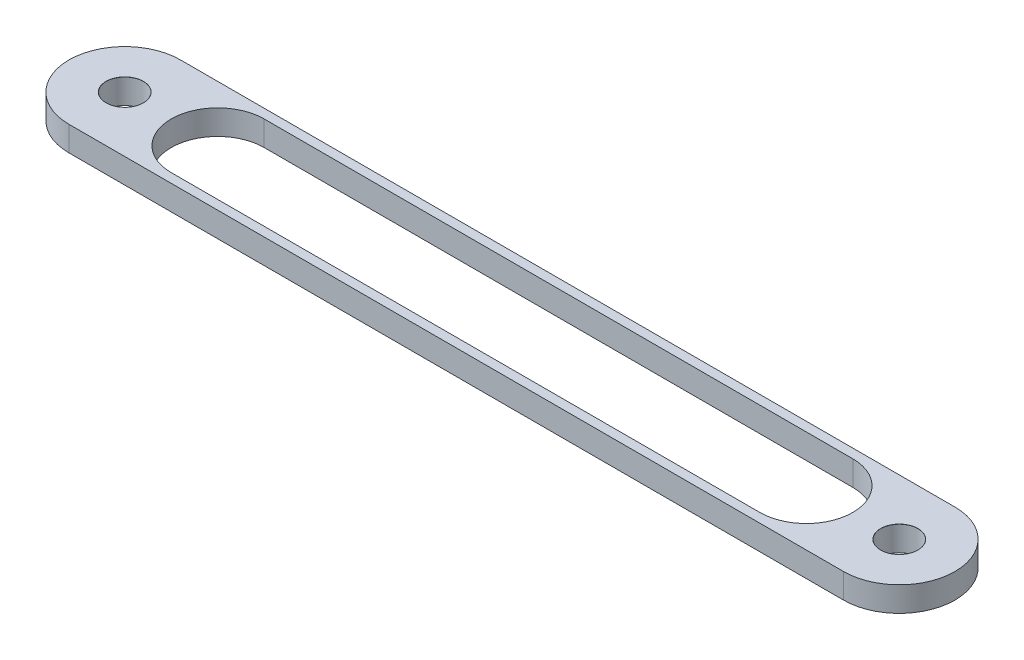
SolidWorks part; units mm, degrees
ref_plane "Plan de face" through (0, 0, 0) normal (0, 0, 1) x (1, 0, 0)
ref_plane "Plan de dessus" through (0, 0, 0) normal (0, 1, 0) x (1, 0, 0)
ref_plane "Plan de droite" through (0, 0, 0) normal (1, 0, 0) x (0, 0, -1)
sketch "Esquisse1" plane through (0, 0, 0) normal (0, 1, 0) x (1, 0, 0)
  line L0 (0, 18) -> (250, 18)
  line L1 (0, -18) -> (250, -18)
  line L2 (30, 15) -> (220, 15)
  line L3 (30, -15) -> (220, -15)
  line L4 (0, 0) -> (30, 0) construction
  arc A0 (0, 18) -> (0, -18) centre (0, 0) ccw
  arc A1 (250, -18) -> (250, 18) centre (250, 0) ccw
  arc A2 (30, 15) -> (30, -15) centre (30, 0) ccw
  arc A3 (220, -15) -> (220, 15) centre (220, 0) ccw
  dimension "D1" = 18
  dimension "D4" = 15
  dimension "D7" = 15
  dimension "D2" = 250
  dimension "D3" = 250
  dimension "D5" = 30
  dimension "D6" = 30
extrude "Boss.-Extru.1" add sketch "Esquisse1" along normal mid plane 8
sketch "Esquisse2" plane through (0, 4, 0) normal (0, 1, 0) x (1, 0, 0)
  line L0 (15, 0) -> (0, 0) construction
  line L1 (235, 0) -> (250, 0) construction
  arc A0 (30, 15) -> (30, -15) centre (30, 0) ccw construction
  arc A1 (220, -15) -> (220, 15) centre (220, 0) ccw construction
  point P1 (0, 0)
  point P7 (250, 0)
  point P15 (0, 0)
  point P18 (250, 0)
hole_wizard "Dégagement M101" positions "Esquisse2" profile "Esquisse4" hole size "M10" standard "ISO" end condition through all
sketch "Esquisse4" plane through (250, 4, 0) normal (1, 0, 0) x (0, 0, 1)
  line L0 (0, 0) -> (0, 8)
  line L1 (0, 8) -> (6, 8)
  line L2 (6, 8) -> (6, 0.025)
  line L3 (6, 0.025) -> (6.025, 0)
  line L5 (6.025, 0) -> (0, 0)
  line L6 (-6, 0.025) -> (-6.025, 0) construction
  line L11 (0, -6.35) -> (0, 107.95) construction
  dimension "Diamètre du perçage jusqu'au prochain" = 12
  dimension "Profondeur du perçage jusqu'au prochain" = 8
  dimension "Diamètre du fraisage entrant" = 12.05
  dimension "Angle du fraisage entrant" = 90
